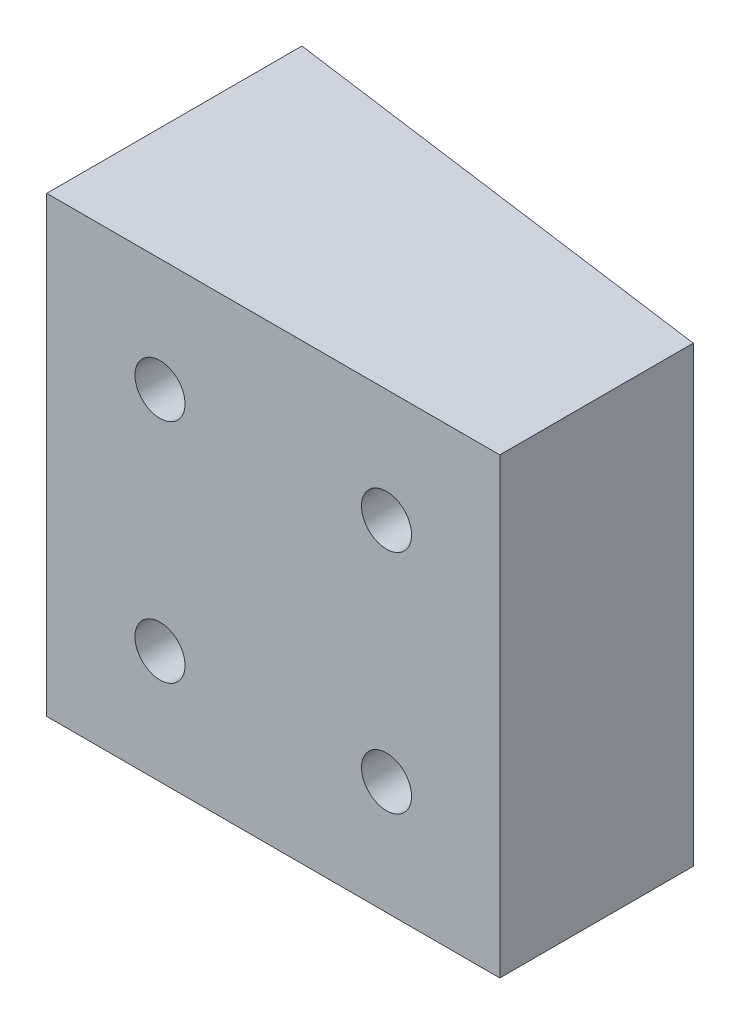
SolidWorks part; units mm, degrees
ref_plane "Front Plane" through (0, 0, 0) normal (0, 0, 1) x (1, 0, 0)
ref_plane "Top Plane" through (0, 0, 0) normal (0, 1, 0) x (1, 0, 0)
ref_plane "Right Plane" through (0, 0, 0) normal (1, 0, 0) x (0, 0, -1)
sketch "Sketch1" plane through (0, 0, 0) normal (0, 1, 0) x (1, 0, 0)
  line L0 (114.3, 0) -> (-152.4, 0) construction
  line L1 (-91.8318, 41.1109) -> (140.9711, 9.4194) construction
  line L2 (50.8, 0) -> (0, 0)
  line L3 (0, 28.6098) -> (50.8, 21.6944)
  line L5 (0, 0) -> (50.8, 0)
  line L6 (0, 0) -> (0, 28.6098)
  line L8 (50.8, 0) -> (50.8, 21.6944)
  dimension "D1" = 50.8
extrude "Boss-Extrude1" add sketch "Sketch1" along normal blind 50.8 contours L2 L8 L3 L6 region at (24.2361, 0, -12.6553)
sketch "Sketch2" plane through (0, 0, 0) normal (0, 0, 1) x (1, 0, 0)
  line L5 (0, 50.8) -> (50.8, 0) construction
  line L6 (0, 0) -> (50.8, 50.8) construction
  line L13 (12.7, 12.7) -> (38.1, 12.7) construction
  line L14 (38.1, 12.7) -> (38.1, 38.1) construction
  line L15 (38.1, 38.1) -> (12.7, 38.1) construction
  line L16 (12.7, 38.1) -> (12.7, 12.7) construction
  dimension "D1" = 25.4
  dimension "D2" = 25.4
hole_wizard "CSK for #10 Flat Head Machine Screw (100)1" positions "Sketch3" profile "Sketch4" countersink size "#10" standard "ANSI Inch" end condition through all
sketch "Sketch3" plane through (320.742, -316.3951, -35.56) normal (0, 0, 1) x (1, 0, 0)
  point P0 (-308.0419, 227.4951)
  point P2 (-308.0419, 252.8951)
  point P4 (-308.042, 329.0951)
  point P6 (-308.042, 354.4951)
sketch "Sketch4" plane through (12.7001, -88.9, -35.56) normal (1, 0, 0) x (0, 1, 0)
  line L0 (0, 0) -> (0, 35.56)
  line L1 (0, 35.56) -> (2.8067, 35.56)
  line L2 (2.8067, 35.56) -> (2.8067, 6.0833)
  line L3 (2.8067, 6.0833) -> (8.89, 0)
  line L4 (8.89, 0) -> (0, 0)
  line L5 (-2.8067, 6.0833) -> (-8.89, 0) construction
  line L6 (0, -6.35) -> (0, 107.95) construction
  dimension "Thru Hole Dia." = 5.6134
  dimension "Thru Hole Depth" = 35.56
  dimension "Near C'Sink Dia." = 17.78
  dimension "Near C'Sink Angle" = 90
hole_wizard "CSK for #10 Flat Head Machine Screw (100)2" positions "Sketch5" profile "Sketch6" countersink size "#10" standard "ANSI Inch" end condition through all
sketch "Sketch5" plane through (320.742, -316.3951, -33.02) normal (0, 0, 1) x (1, 0, 0)
  point P0 (-282.6419, 227.4951)
  point P2 (-282.6419, 252.8951)
  point P4 (-282.642, 329.0951)
  point P6 (-282.642, 354.4951)
sketch "Sketch6" plane through (38.1001, -88.9, -33.02) normal (1, 0, 0) x (0, 1, 0)
  line L0 (0, 0) -> (0, 33.02)
  line L1 (0, 33.02) -> (2.8067, 33.02)
  line L2 (2.8067, 33.02) -> (2.8067, 6.0833)
  line L3 (2.8067, 6.0833) -> (8.89, 0)
  line L4 (8.89, 0) -> (0, 0)
  line L5 (-2.8067, 6.0833) -> (-8.89, 0) construction
  line L6 (0, -6.35) -> (0, 107.95) construction
  dimension "Thru Hole Dia." = 5.6134
  dimension "Thru Hole Depth" = 33.02
  dimension "Near C'Sink Dia." = 17.78
  dimension "Near C'Sink Angle" = 90
